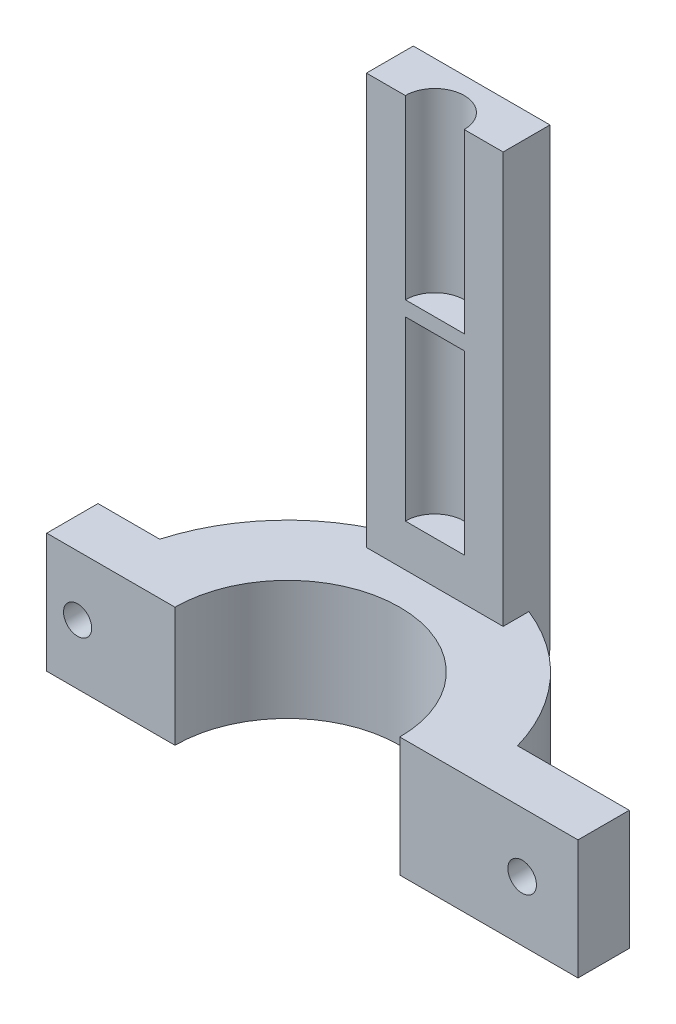
SolidWorks part; units mm, degrees
ref_plane "前基準面" through (0, 0, 0) normal (0, 0, 1) x (1, 0, 0)
ref_plane "上基準面" through (0, 0, 0) normal (0, 1, 0) x (1, 0, 0)
ref_plane "右基準面" through (0, 0, 0) normal (1, 0, 0) x (0, 0, -1)
sketch "草圖1" plane through (0, 0, 0) normal (0, 1, 0) x (1, 0, 0)
  line L1 (-15.75, 7.075) -> (15.75, 7.075)
  line L2 (-15.75, 7.075) -> (-15.75, -7.075)
  line L3 (-15.75, -7.075) -> (15.75, -7.075)
  line L4 (15.75, 7.075) -> (15.75, -7.075)
  line L5 (-15.75, 7.075) -> (15.75, -7.075) construction
  line L6 (-15.75, -7.075) -> (15.75, 7.075) construction
  point P0 (0, 0)
  dimension "D1" = 14.15
  dimension "D2" = 31.5
extrude "伸長-薄件1" add sketch "草圖1" along normal blind 12.25 thin thin type one direction wall 10
sketch "草圖2" plane through (0, 12.25, 0) normal (0, 1, 0) x (1, 0, 0)
  line L0 (-1014.255, 0) -> (48985.745, 0) construction
  line L1 (-15.75, 7.075) -> (-15.75, -7.075) construction
  line L2 (-20.75, -988.4004) -> (-20.75, 49011.5996) construction
  line L3 (-25.75, 17.075) -> (-20.75, 17.075) construction
  line L4 (-25.75, 17.075) -> (-25.75, 11.5996) construction
  line L5 (-25.75, 11.5996) -> (-20.75, 11.5996) construction
  line L6 (-20.75, 17.075) -> (-20.75, 11.5996) construction
  line L7 (25.75, 17.075) -> (20.75, 17.075) construction
  line L8 (25.75, 17.075) -> (25.75, 12.4477) construction
  line L9 (25.75, 12.4477) -> (20.75, 12.4477) construction
  line L10 (20.75, 17.075) -> (20.75, 12.4477) construction
  line L11 (20.75, -987.5523) -> (20.75, 49012.4477) construction
  circle A0 centre (-20.75, 0) radius 1.91
  circle A1 centre (20.75, 0) radius 1.91
  point P5 (-15.75, 0)
  dimension "D3" = 3.82
  dimension "D4" = 3.82
  dimension "D1" = 5
  dimension "D2" = 5
extrude "除料-伸長1" cut sketch "草圖2" against normal through all
sketch "草圖4" plane through (0, 0, 0) normal (0, -1, 0) x (1, 0, 0)
  line L0 (-1000, 0) -> (49000, 0) construction
  line L1 (25.75, 17.075) -> (25.75, -17.075) construction
  line L2 (12.75, 6.955) -> (25.75, 6.955)
  line L3 (12.75, 6.955) -> (12.75, -6.955)
  line L4 (12.75, -6.955) -> (25.75, -6.955)
  line L5 (25.75, 6.955) -> (25.75, -6.955)
  line L6 (12.75, 6.955) -> (25.75, -6.955) construction
  line L7 (12.75, -6.955) -> (25.75, 6.955) construction
  point P1 (19.25, 0)
  dimension "D1" = 13.91
  dimension "D2" = 13
extrude "填料-伸長1" add sketch "草圖4" along normal blind 74.82
sketch "草圖5" plane through (12.75, 0, 0) normal (-1, 0, 0) x (0, 0, 1)
  line L0 (6.955, -74.82) -> (6.955, 0) construction
  line L1 (-6.955, -74.82) -> (6.955, -74.82)
  line L2 (-6.955, -74.82) -> (-6.955, -58.59)
  line L3 (-6.955, -58.59) -> (6.955, -58.59)
  line L4 (6.955, -74.82) -> (6.955, -58.59)
  dimension "D1" = 16.23
extrude "填料-伸長2" add sketch "草圖5" along normal blind 16
sketch "草圖7" plane through (3.6267, -74.82, 0) normal (0, -1, 0) x (1, 0, 0)
  circle A0 centre (-30.9782, 0) radius 15.25
  dimension "D1" = 30.5
extrude "伸長-薄件2" add sketch "草圖7" against normal blind 16.23 thin thin type one direction wall 10
ref_plane "平面1" through (-60, 0, 0) normal (1, 0, 0) x (0, 0, -1)
ref_plane "平面2" through (-55, 0, 0) normal (1, 0, 0) x (0, 0, -1)
ref_plane "平面3" through (-60, 0, 0) normal (1, 0, 0) x (0, 0, -1)
ref_plane "平面4" through (-60, 0, 0) normal (1, 0, 0) x (0, 0, -1)
sketch "草圖16" plane through (-60, 0, 0) normal (1, 0, 0) x (0, 0, -1)
  line L1 (6.955, -58.59) -> (-6.955, -58.59)
  line L2 (6.955, -58.59) -> (6.955, -74.82)
  line L3 (6.955, -74.82) -> (-6.955, -74.82)
  line L4 (-6.955, -58.59) -> (-6.955, -74.82)
extrude "填料-伸長4" add sketch "草圖16" along normal blind 10
sketch "草圖17" plane through (0, 0, -6.955) normal (0, 0, -1) x (-1, 0, 0)
  line L0 (-948.3753, -66.705) -> (49051.6247, -66.705) construction
  line L1 (51.6247, -74.82) -> (51.6247, -58.59) construction
  line L2 (55.8124, -1058.59) -> (55.8124, 48941.41) construction
  line L3 (51.6247, -58.59) -> (60, -58.59) construction
  circle A0 centre (55.8124, -66.705) radius 1.91
  point P5 (51.6247, -66.705)
  point P10 (55.8124, -58.59)
  dimension "D1" = 3.82
extrude "除料-伸長7" cut sketch "草圖17" against normal through all
sketch "草圖19" plane through (0, -58.59, 0) normal (0, 1, 0) x (1, 0, 0)
  line L0 (-60, 6.955) -> (-60, -6.955) construction
  line L1 (-60, 0) -> (36.5445, 0)
  line L2 (-60, 0) -> (-60, -28.4267)
  line L3 (-60, -28.4267) -> (36.5445, -28.4267)
  line L4 (36.5445, 0) -> (36.5445, -28.4267)
extrude "除料-伸長8" cut sketch "草圖19" against normal blind 41 and the other way blind 83
sketch "草圖21" plane through (25.75, 0, 0) normal (1, 0, 0) x (0, 0, -1)
  line L0 (0, -74.82) -> (0, 12.25) construction
  line L1 (0, -36.2363) -> (18.5662, -36.2363)
  line L2 (0, -36.2363) -> (0, 14.4577)
  line L3 (0, 14.4577) -> (18.5662, 14.4577)
  line L4 (18.5662, -36.2363) -> (18.5662, 14.4577)
extrude "除料-伸長10" cut sketch "草圖21" against normal blind 57
sketch "草圖22" plane through (0, -36.2363, 0) normal (0, 1, 0) x (1, 0, 0)
  line L1 (12.75, 0) -> (25.75, 0)
  line L2 (12.75, 0) -> (12.75, 6.955)
  line L3 (12.75, 6.955) -> (25.75, 6.955)
  line L4 (25.75, 0) -> (25.75, 6.955)
extrude "除料-伸長11" cut sketch "草圖22" against normal blind 57
ref_plane "平面5" through (0, 0, -30) normal (0, 0, 1) x (1, 0, 0)
sketch "草圖23" plane through (0, 0, -30) normal (0, 0, 1) x (1, 0, 0)
  line L0 (-27.3515, -1058.59) -> (-27.3515, 48941.41) construction
  line L1 (-3.0782, -58.59) -> (-51.6247, -58.59) construction
  line L2 (-3.0782, -74.82) -> (-3.0782, -58.59) construction
  line L3 (-18.0782, -28.8448) -> (-36.6247, -28.8448)
  line L4 (-18.0782, -28.8448) -> (-18.0782, -71.3448)
  line L5 (-18.0782, -71.3448) -> (-36.6247, -71.3448)
  line L6 (-36.6247, -28.8448) -> (-36.6247, -71.3448)
  line L7 (-51.6247, -74.82) -> (-51.6247, -58.59) construction
  point P5 (-27.3515, -58.59)
  dimension "D1" = 15
  dimension "D2" = 15
  dimension "D3" = 42.5
extrude "填料-伸長6" add sketch "草圖23" along normal blind 10 and the other way blind 5
sketch "草圖24" plane through (0, -28.8448, 0) normal (0, 1, 0) x (1, 0, 0)
  line L0 (-18.0782, 20) -> (-36.6247, 20) construction
  circle A0 centre (-27.3515, 20) radius 4
  dimension "D1" = 8
extrude "除料-伸長12" cut sketch "草圖24" against normal blind 24
sketch "草圖26" plane through (0, -28.8448, 0) normal (0, 1, 0) x (1, 0, 0)
  line L0 (-36.6247, 35) -> (-36.6247, 20) construction
  line L1 (-18.0782, 35) -> (-36.6247, 35)
  line L2 (-18.0782, 35) -> (-18.0782, 26.3584)
  line L3 (-18.0782, 26.3584) -> (-36.6247, 26.3584)
  line L4 (-36.6247, 35) -> (-36.6247, 26.3584)
extrude "除料-伸長13" cut sketch "草圖26" against normal through all
fillet "圓角1" radius 10 1 edges at (-27.3515, -71.3448, -26.3584)
sketch "草圖27" plane through (0, 0, -6.955) normal (0, 0, -1) x (-1, 0, 0)
  line L0 (3.0782, -74.82) -> (-12.75, -74.82) construction
  line L1 (-12.75, -58.59) -> (-12.08, -58.59)
  line L2 (-12.75, -58.59) -> (-12.75, -74.82)
  line L3 (-12.75, -74.82) -> (-12.08, -74.82)
  line L4 (-12.08, -58.59) -> (-12.08, -74.82)
  dimension "D1" = 0.67
extrude "除料-伸長14" cut sketch "草圖27" against normal blind 10
sketch "草圖28" plane through (0, -28.8448, 0) normal (0, 1, 0) x (1, 0, 0)
  line L1 (-18.0782, 20) -> (-36.6247, 20)
  line L2 (-18.0782, 20) -> (-18.0782, 26.3584)
  line L3 (-18.0782, 26.3584) -> (-36.6247, 26.3584)
  line L4 (-36.6247, 20) -> (-36.6247, 26.3584)
extrude "填料-伸長7" add sketch "草圖28" along normal blind 26
sketch "草圖29" plane through (0, -2.8448, 0) normal (0, 1, 0) x (1, 0, 0)
  line L0 (-36.6247, 20) -> (-18.0782, 20) construction
  circle A0 centre (-27.3515, 20) radius 4
  dimension "D1" = 8
extrude "除料-伸長15" cut sketch "草圖29" against normal blind 24
sketch "草圖30" plane through (0, 0, -6.955) normal (0, 0, -1) x (-1, 0, 0)
  line L0 (-4.5009, -1058.59) -> (-4.5009, 48941.41) construction
  line L1 (3.0782, -58.59) -> (-12.08, -58.59) construction
  line L2 (-1012.08, -66.705) -> (48987.92, -66.705) construction
  line L3 (-12.08, -74.82) -> (-12.08, -58.59) construction
  circle A0 centre (-4.5009, -66.705) radius 1.94
  point P5 (-4.5009, -58.59)
  point P10 (-12.08, -66.705)
  dimension "D1" = 3.88
extrude "除料-伸長16" cut sketch "草圖30" against normal blind 24
